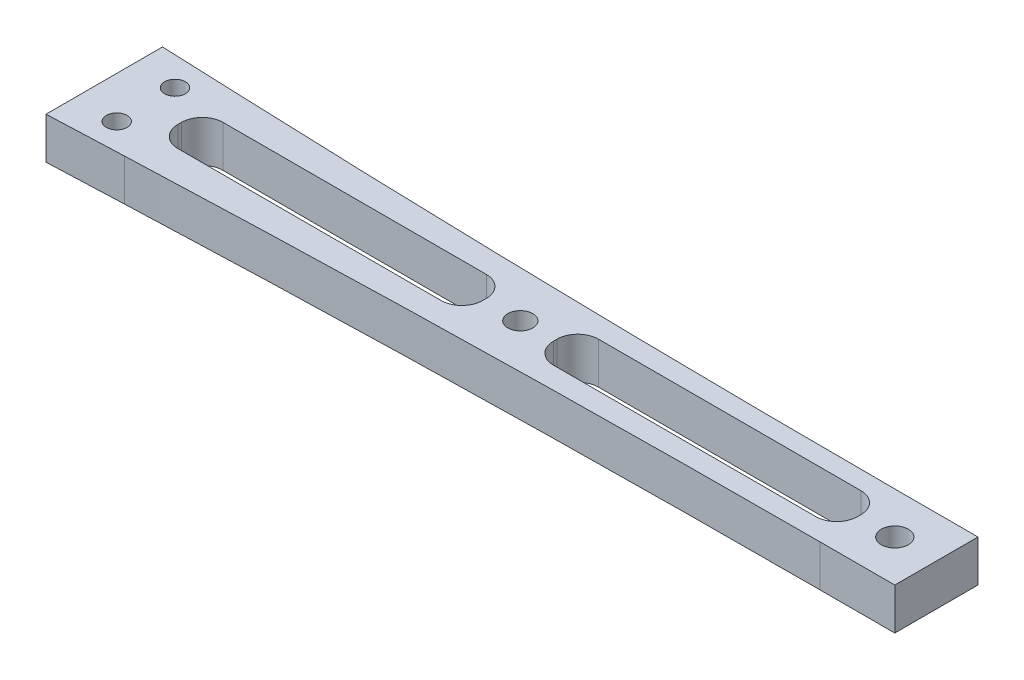
SolidWorks part; units mm, degrees
material "6061 Alloy"
ref_plane "Płaszczyzna przednia" through (0, 0, 0) normal (0, 0, 1) x (1, 0, 0)
ref_plane "Płaszczyzna górna" through (0, 0, 0) normal (0, 1, 0) x (1, 0, 0)
ref_plane "Płaszczyzna prawa" through (0, 0, 0) normal (1, 0, 0) x (0, 0, -1)
sketch "Szkic1" plane through (0, 0, 0) normal (0, 1, 0) x (1, 0, 0)
  line L0 (100, 0) -> (100, 10)
  line L4 (200, 0) -> (200, 20)
  line L5 (0, 10) -> (10, 10)
  line L6 (200, 10) -> (190, 10)
  line L8 (22.9848, 15.5746) -> (86.2594, 15.5746)
  line L9 (17.9848, 10.5746) -> (17.9848, 9.6967)
  line L10 (22.9848, 4.6967) -> (86.2594, 4.6967)
  line L11 (91.2594, 10.5746) -> (91.2594, 9.6967)
  line L12 (113.2251, 15.5746) -> (176.2862, 15.5746)
  line L13 (108.2251, 10.5746) -> (108.2251, 9.7528)
  line L14 (113.2251, 4.7528) -> (176.2862, 4.7528)
  line L15 (181.2862, 10.5746) -> (181.2862, 9.7528)
  line L16 (10, 3) -> (10, 17)
  line L17 (0, -4) -> (100, 0)
  line L18 (200, 0) -> (100, 0)
  line L19 (200, 20) -> (100, 20)
  line L20 (100, 20) -> (0, 24)
  line L21 (0, 24) -> (0, -4)
  circle A0 centre (100, 10) radius 3
  circle A2 centre (190, 10) radius 3.25
  arc A3 (176.2862, 4.7528) -> (181.2862, 9.7528) centre (176.2862, 9.7528) ccw
  arc A4 (181.2862, 10.5746) -> (176.2862, 15.5746) centre (176.2862, 10.5746) ccw
  arc A5 (113.2251, 4.7528) -> (108.2251, 9.7528) centre (113.2251, 9.7528) cw
  arc A6 (113.2251, 15.5746) -> (108.2251, 10.5746) centre (113.2251, 10.5746) ccw
  arc A7 (17.9848, 9.6967) -> (22.9848, 4.6967) centre (22.9848, 9.6967) ccw
  arc A8 (86.2594, 4.6967) -> (91.2594, 9.6967) centre (86.2594, 9.6967) ccw
  arc A9 (91.2594, 10.5746) -> (86.2594, 15.5746) centre (86.2594, 10.5746) ccw
  arc A10 (22.9848, 15.5746) -> (17.9848, 10.5746) centre (22.9848, 10.5746) ccw
  circle A11 centre (10, 17) radius 2.5
  circle A12 centre (10, 3) radius 2.5
  point P39 (0, 10)
  point P42 (10, 10)
  dimension "D1" = 5
extrude "Dodanie-wyciągnięcie1" add sketch "Szkic1" along normal blind 10 contours A0 L4 region at (49.9193, 0, -0.0179)
fillet "Zaokrąglenie1" radius 4100 2 edges at (100, 5, -20) (100, 5, 0)
